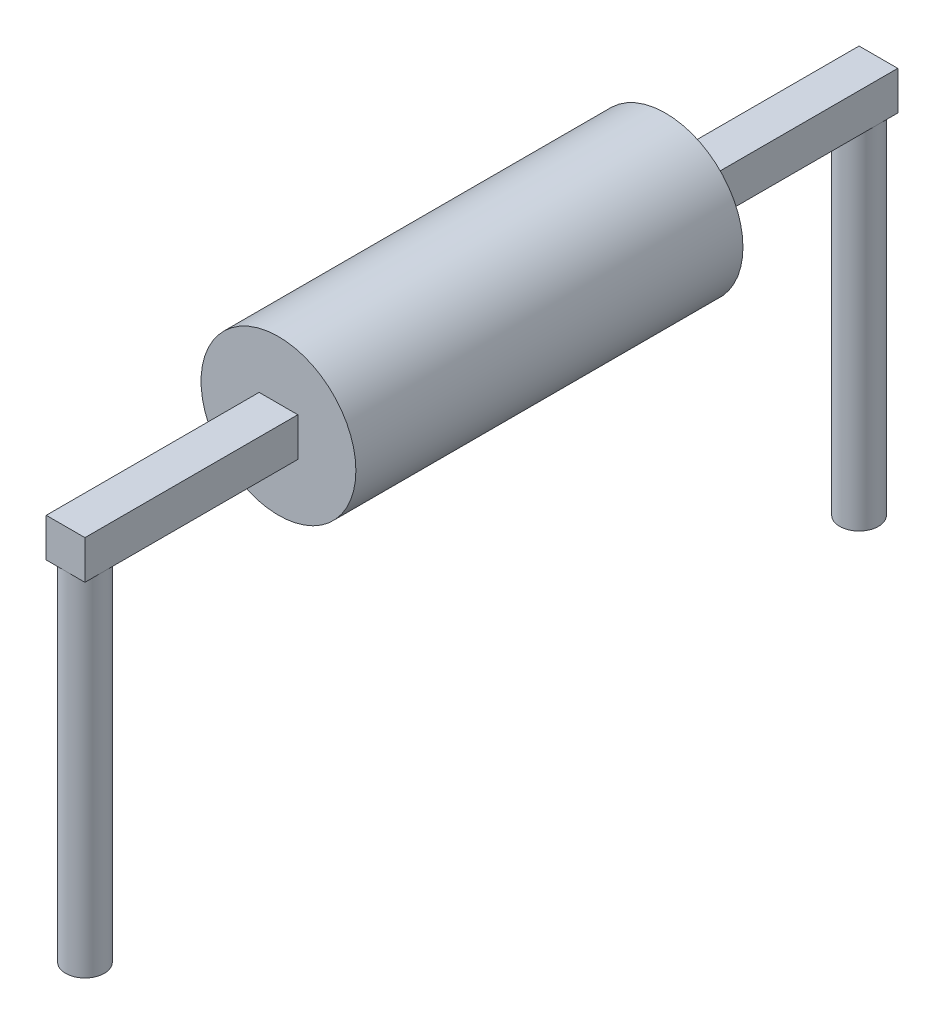
SolidWorks part; units mm, degrees
ref_plane "Спереди" through (0, 0, 0) normal (0, 0, 1) x (1, 0, 0)
ref_plane "Сверху" through (0, 0, 0) normal (0, 1, 0) x (1, 0, 0)
ref_plane "Справа" through (0, 0, 0) normal (1, 0, 0) x (0, 0, -1)
sketch "Эскиз1" plane through (0, 0, 0) normal (0, 0, 1) x (1, 0, 0)
  circle A0 centre (0, 0) radius 1
  dimension "D1" = 2
extrude "Вытянуть1" add sketch "Эскиз1" along normal blind 5
sketch "Эскиз2" plane through (0, 0, 5) normal (0, 0, 1) x (1, 0, 0)
  line L0 (-0.0001, 0.6747) -> (-0.0001, -0.3959) construction
  line L1 (-0.2501, -0.25) -> (0.2499, -0.25)
  line L2 (-0.2501, -0.25) -> (-0.2501, 0.25)
  line L3 (-0.2501, 0.25) -> (0.2499, 0.25)
  line L4 (0.2499, -0.25) -> (0.2499, 0.25)
  line L5 (-0.474, 0) -> (0.6636, 0) construction
  dimension "D2" = 0.5
extrude "Вытянуть2" add sketch "Эскиз2" along normal blind 2.75 and the other way blind 7.75
sketch "Эскиз3" plane through (0, -0.25, 0) normal (0, -1, 0) x (1, 0, 0)
  line L0 (0, 5) -> (0, 0) construction
  line L1 (-0.2501, 7.75) -> (0.2499, 7.75) construction
  line L2 (-0.2501, -2.75) -> (0.2499, -2.75) construction
  circle A0 centre (0, 7.5) radius 0.25
  circle A1 centre (0, -2.5) radius 0.25
  dimension "D1" = 0.5
extrude "Вытянуть3" add sketch "Эскиз3" along normal blind 4.5
